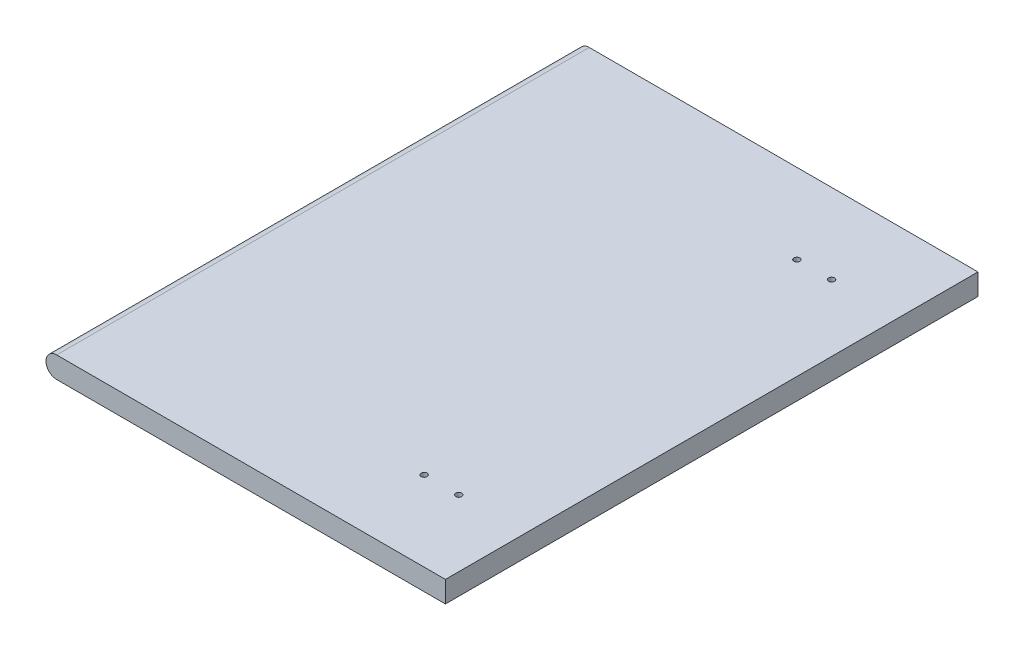
SolidWorks part; units mm, degrees
ref_plane "Front Plane" through (0, 0, 0) normal (0, 0, 1) x (1, 0, 0)
ref_plane "Top Plane" through (0, 0, 0) normal (0, 1, 0) x (1, 0, 0)
ref_plane "Right Plane" through (0, 0, 0) normal (1, 0, 0) x (0, 0, -1)
other "Bounding Box"
ref_plane "Default Plane" through (-150, 0, -200) normal (1, 0, 0) x (0, 0, -1)
sketch "Sketch1" plane through (0, 0, 0) normal (0, 1, 0) x (1, 0, 0)
  line L1 (-150, -200) -> (150, -200)
  line L2 (-150, -200) -> (-150, 200)
  line L3 (-150, 200) -> (150, 200)
  line L4 (150, -200) -> (150, 200)
  line L5 (-150, -200) -> (150, 200) construction
  line L6 (-150, 200) -> (150, -200) construction
  point P0 (0, 0)
  dimension "D1" = 300
  dimension "D2" = 400
extrude "Boss-Extrude1" add sketch "Sketch1" along normal blind 16
sketch "Sketch3" plane through (0, 16, 0) normal (0, 1, 0) x (1, 0, 0)
  line L4 (150, 200) -> (-150, 200) construction
  line L5 (-150, -200) -> (-110, -200)
  line L6 (-150, -200) -> (-150, 200)
  line L7 (-150, 200) -> (-110, 200)
  line L12 (-110, -200) -> (-110, 200)
  dimension "D1" = 40
extrude "Boss-Extrude4" [suppressed] add sketch "Sketch3" along normal blind 16
chamfer "Chamfer2" [suppressed] distance 10 angle 45
hole_wizard "CSK for #8 Flat Head Machine Screw (100)1" positions "Sketch9" profile "Sketch8" countersink size "#8" standard "ANSI Inch"
sketch "Sketch9" plane through (0, 0, 0) normal (0, -1, 0) x (-1, 0, 0)
  line L0 (-150, -200) -> (-150, 200) construction
  line L1 (150, -200) -> (-150, -200) construction
  point P0 (-100, -140)
  point P2 (-74, -140)
  dimension "D1" = 50
  dimension "D2" = 26
  dimension "D3" = 60
sketch "Sketch8" plane through (100, 0, 140) normal (1, 0, 0) x (0, 0, -1)
  line L0 (0, 0) -> (0, 26.3507)
  line L1 (0, 26.3507) -> (2.2479, 25)
  line L2 (2.2479, 25) -> (2.2479, 1.6518)
  line L3 (2.2479, 1.6518) -> (4.2164, 0)
  line L5 (4.2164, 0) -> (0, 0)
  line L6 (-2.2479, 1.6518) -> (-4.2164, 0) construction
  line L10 (0, 26.3507) -> (-2.2479, 25) construction
  line L11 (0, -6.35) -> (0, 107.95) construction
  dimension "Hole Dia." = 4.4958
  dimension "Hole Depth" = 25
  dimension "Near C'Sink Dia." = 8.4328
  dimension "Near C'Sink Angle" = 100
  dimension "Drill Angle" = 118
mirror "Mirror1" about plane through (0, 0, 0) normal (0, 0, 1) of "CSK for #8 Flat Head Machine Screw (100)1"
fillet "Fillet1" radius 8 2 edges at (-150, 16, 0) (-150, 0, 0)
